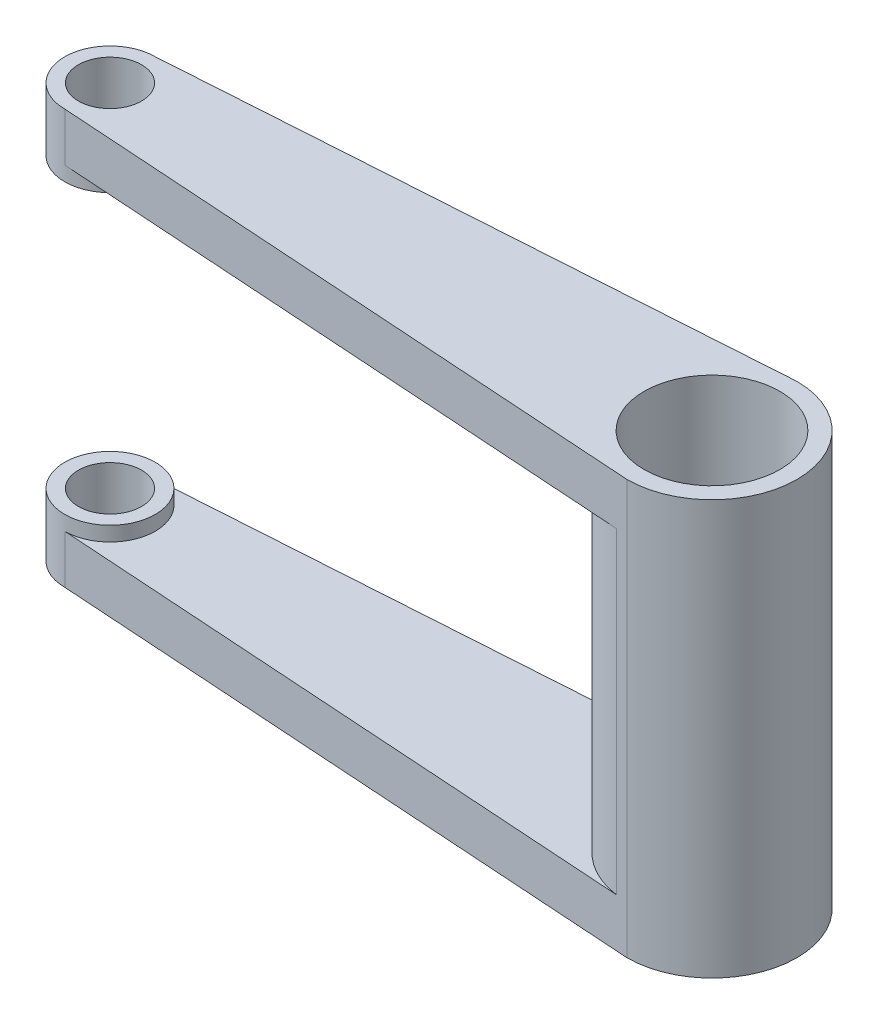
SolidWorks part; units mm, degrees
ref_plane "Alzado" through (0, 0, 0) normal (0, 0, 1) x (1, 0, 0)
ref_plane "Planta" through (0, 0, 0) normal (0, 1, 0) x (1, 0, 0)
ref_plane "Vista lateral" through (0, 0, 0) normal (1, 0, 0) x (0, 0, -1)
sketch "Croquis5" plane through (0, 0, 0) normal (0, 0, 1) x (1, 0, 0)
  line L0 (3.1177, -1.0799) -> (103.1129, -2.0591) construction
  dimension "D1" = 100
sketch "Croquis6" plane through (0, 0, 0) normal (0, 1, 0) x (1, 0, 0)
  line L0 (188.1262, -9.2464) -> (288.071, -5.9247) construction
  dimension "D1" = 100
sketch "Croquis8" plane through (0, 0, 0) normal (0, 0, 1) x (1, 0, 0)
  line L0 (147.4505, 85.6626) -> (147.4505, 0) construction
  line L1 (112.4505, 0) -> (112.4505, 85.6626) construction
  line L2 (129.9505, 85.6626) -> (129.9505, -0.3374) construction
  line L3 (5.9505, 86.362) -> (5.9505, 2.362) construction
  line L4 (202.3444, 42.6626) -> (-39.5908, 42.6626) construction
  point P8 (0, 0)
  point P13 (129.9505, 42.6626)
  dimension "D1" = 35
  dimension "D2" = 17.5
  dimension "D3" = 124
  dimension "D4" = 86
  dimension "D5" = 84
sketch "Croquis11" plane through (0, 0, 0) normal (0, 1, 0) x (1, 0, 0)
  line L0 (129.9505, 0) -> (5.9505, 0) construction
  line L1 (5.9505, -9.3207) -> (129.9505, -17.5)
  line L2 (5.9505, 9.3207) -> (129.9505, 17.5)
  circle A0 centre (129.9505, 0) radius 17.5
  circle A1 centre (129.9505, 0) radius 13.9749
  circle A2 centre (5.9505, 0) radius 9.3207
  circle A3 centre (5.9505, 0) radius 6.4989
extrude "Saliente-Extruir7" add sketch "Croquis11" along normal blind 13 contours A2 A3 region at (-3.1066, 0, 0)
extrude "Saliente-Extruir8" add sketch "Croquis11<13>" along normal blind 10 contours A0 L0 A2 L1 | L0 A0 L2 A2 region at (68.9239, 0, -6.9712) region at (68.9239, 0, 6.9712)
sketch "Croquis11<13>" plane through (0, 0, 0) normal (0, 1, 0) x (1, 0, 0) same geometry as "Croquis11"
extrude "Saliente-Extruir9" add sketch "Croquis11<17>" along normal up to vertex (42.6626 mm away) contours A1 A0 L1 L2 region at (112.9455, 0, 0) up to point (129.9505, 42.6626, 0)
sketch "Croquis11<17>" plane through (0, 0, 0) normal (0, 1, 0) x (1, 0, 0) same geometry as "Croquis11"
mirror "Simetría3" about plane through (0, 42.6626, 0) normal (0, 1, 0) of bodies 108
